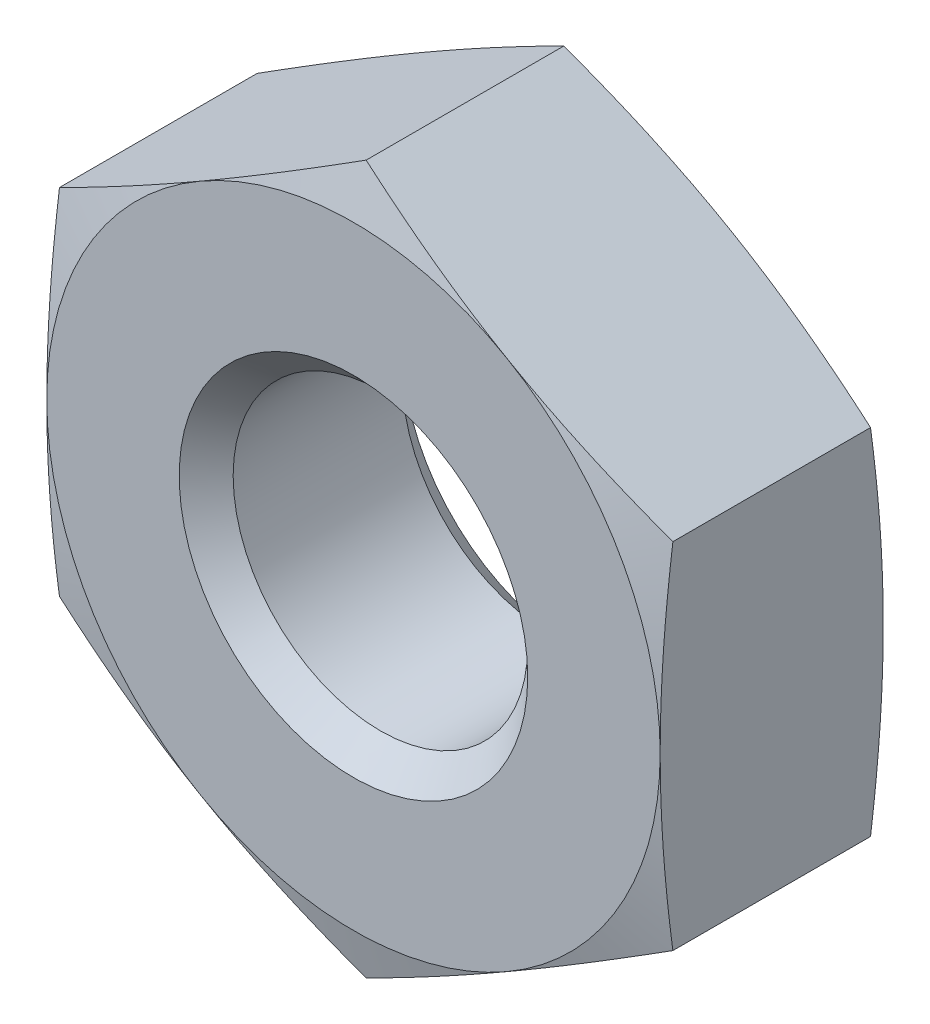
SolidWorks part; units mm, degrees
material "Plain Carbon Steel"
ref_plane "Front Plane" through (0, 0, 0) normal (0, 0, 1) x (1, 0, 0)
ref_plane "Top Plane" through (0, 0, 0) normal (0, 1, 0) x (1, 0, 0)
ref_plane "Right Plane" through (0, 0, 0) normal (1, 0, 0) x (0, 0, -1)
sketch "Sketch1" plane through (0, 0, 0) normal (1, 0, 0) x (0, 0, -1)
  line L0 (0, 0) -> (0, 5.588)
  line L1 (0, 5.588) -> (0.2995, 6.7056)
  line L2 (0.2995, 6.7056) -> (3.7645, 6.7056)
  line L3 (3.7645, 6.7056) -> (4.064, 5.588)
  line L4 (4.064, 5.588) -> (4.064, 0)
  line L5 (4.064, 0) -> (0, 0)
  line L6 (4.064, 0) -> (0, 0) construction
sketch "Sketch2" plane through (0, 0, 0) normal (0, 0, 1) x (1, 0, 0)
  line L0 (-11.176, 11.176) -> (-11.176, -11.176)
  line L1 (-11.176, -11.176) -> (11.176, -11.176)
  line L2 (11.176, -11.176) -> (11.176, 11.176)
  line L3 (11.176, 11.176) -> (-11.176, 11.176)
  line L4 (-5.588, 3.2262) -> (-5.588, -3.2262)
  line L5 (-5.588, -3.2262) -> (0, -6.4525)
  line L6 (0, -6.4525) -> (5.588, -3.2262)
  line L7 (5.588, -3.2262) -> (5.588, 3.2262)
  line L8 (5.588, 3.2262) -> (0, 6.4525)
  line L9 (0, 6.4525) -> (-5.588, 3.2262)
revolve "Revolve1" add sketch "Sketch1" angle 360 about L6 reverse direction yes
extrude "Cut-Extrude1" cut sketch "Sketch2" against normal blind 4.064
sketch "Sketch3" plane through (0, 0, 0) normal (1, 0, 0) x (0, 0, -1)
  line L0 (0, 0) -> (0, 3.175)
  line L1 (0, 3.175) -> (0.4915, 2.6835)
  line L2 (0.4915, 2.6835) -> (3.5725, 2.6835)
  line L3 (3.5725, 2.6835) -> (4.064, 3.175)
  line L4 (4.064, 3.175) -> (4.064, 0)
  line L5 (4.064, 0) -> (0, 0)
  line L6 (4.064, 0) -> (0, 0) construction
revolve "Cut-Revolve1" cut sketch "Sketch3" angle 360 about L6 reverse direction yes
cosmetic thread "Cosmetic Thread1" parameters "D1"=4.064, "D2"=6.35
ref_plane "NUT XY" through (0, 0, 0) normal (0, 0, 1) x (1, 0, 0)
ref_plane "NUT XZ" through (0, 0, 0) normal (0, -1, 0) x (-1, 0, 0)
ref_plane "NUT YZ" through (0, 0, 0) normal (1, 0, 0) x (0, 0, -1)
ref_axis "NUT X" through (-80.9, 0, 0) along (1, 0, 0)
ref_axis "NUT Y" through (0, -50, 0) along (0, 1, 0)
ref_axis "NUT Z" through (0, 0, 80.9) along (0, 0, -1)
sketch3d "NUT"
  point P0 (0, 0, 0)
ref_plane "a1 XY" through (0, 0, 0) normal (0, 0, 1) x (1, 0, 0)
ref_plane "a1 XZ" through (0, 5.588, 0) normal (0, -1, 0) x (-1, 0, 0)
ref_plane "a1 YZ" through (-5.588, 0, 0) normal (1, 0, 0) x (0, 0, -1)
ref_axis "a1 X" through (-80.9, 5.588, 0) along (1, 0, 0)
ref_axis "a1 Y" through (-5.588, -50, 0) along (0, 1, 0)
ref_axis "a1 Z" through (-5.588, 5.588, 80.9) along (0, 0, -1)
sketch3d "a1"
  point P0 (-5.588, 5.588, 0)
ref_plane "a2 XY" through (0, 0, 0) normal (0, 0, 1) x (1, 0, 0)
ref_plane "a2 XZ" through (0, 5.588, 0) normal (0, -1, 0) x (-1, 0, 0)
ref_plane "a2 YZ" through (5.588, 0, 0) normal (1, 0, 0) x (0, 0, -1)
ref_axis "a2 X" through (-80.9, 5.588, 0) along (1, 0, 0)
ref_axis "a2 Y" through (5.588, -50, 0) along (0, 1, 0)
ref_axis "a2 Z" through (5.588, 5.588, 80.9) along (0, 0, -1)
sketch3d "a2"
  point P0 (5.588, 5.588, 0)
ref_plane "b1 XY" through (0, 0, 0) normal (1, 0, 0) x (0, 0, -1)
ref_plane "b1 XZ" through (0, 5.588, 0) normal (0, -1, 0) x (-1, 0, 0)
ref_plane "b1 YZ" through (0, 0, 0) normal (0, 0, -1) x (-1, 0, 0)
ref_axis "b1 X" through (0, 5.588, 80.9) along (0, 0, -1)
ref_axis "b1 Y" through (0, -50, 0) along (0, 1, 0)
ref_axis "b1 Z" through (80.9, 5.588, 0) along (-1, 0, 0)
sketch3d "b1"
  point P0 (0, 5.588, 0)
ref_plane "b2 XY" through (0, 0, 0) normal (1, 0, 0) x (0, 0, -1)
ref_plane "b2 XZ" through (0, 5.588, 0) normal (0, -1, 0) x (-1, 0, 0)
ref_plane "b2 YZ" through (0, 0, -4.064) normal (0, 0, -1) x (-1, 0, 0)
ref_axis "b2 X" through (0, 5.588, 80.9) along (0, 0, -1)
ref_axis "b2 Y" through (0, -50, -4.064) along (0, 1, 0)
ref_axis "b2 Z" through (80.9, 5.588, -4.064) along (-1, 0, 0)
sketch3d "b2"
  point P0 (0, 5.588, -4.064)
ref_plane "e XY" through (0, 0, 0) normal (1, 0, 0) x (0, 0, -1)
ref_plane "e XZ" through (0, 0, 0) normal (0, -1, 0) x (-1, 0, 0)
ref_plane "e YZ" through (0, 0, -4.064) normal (0, 0, -1) x (-1, 0, 0)
ref_axis "e X" through (0, 0, 80.9) along (0, 0, -1)
ref_axis "e Y" through (0, -50, -4.064) along (0, 1, 0)
ref_axis "e Z" through (80.9, 0, -4.064) along (-1, 0, 0)
sketch3d "e"
  point P0 (0, 0, -4.064)
ref_plane "ol1 XY" through (0, 0, 0) normal (0, 1, 0) x (1, 0, 0)
ref_plane "ol1 XZ" through (0, 0, -5.588) normal (0, 0, 1) x (1, 0, 0)
ref_plane "ol1 YZ" through (0, 0, 0) normal (1, 0, 0) x (0, 0, -1)
ref_axis "ol1 X" through (-80.9, 0, -5.588) along (1, 0, 0)
ref_axis "ol1 Y" through (0, 0, 50) along (0, 0, -1)
ref_axis "ol1 Z" through (0, 50, -5.588) along (0, -1, 0)
sketch3d "ol1"
  point P0 (0, 0, -5.588)
ref_plane "ol2 XY" through (0, 0, 0) normal (0, 1, 0) x (1, 0, 0)
ref_plane "ol2 XZ" through (0, 0, -5.588) normal (0, 0, 1) x (1, 0, 0)
ref_plane "ol2 YZ" through (4.064, 0, 0) normal (1, 0, 0) x (0, 0, -1)
ref_axis "ol2 X" through (-80.9, 0, -5.588) along (1, 0, 0)
ref_axis "ol2 Y" through (4.064, 0, 50) along (0, 0, -1)
ref_axis "ol2 Z" through (4.064, 50, -5.588) along (0, -1, 0)
sketch3d "ol2"
  point P0 (4.064, 0, -5.588)
ref_plane "th1 XY" through (0, 0, 0) normal (1, 0, 0) x (0, 0, -1)
ref_plane "th1 XZ" through (0, 3.175, 0) normal (0, -1, 0) x (-1, 0, 0)
ref_plane "th1 YZ" through (0, 0, -4.064) normal (0, 0, -1) x (-1, 0, 0)
ref_axis "th1 X" through (0, 3.175, 80.9) along (0, 0, -1)
ref_axis "th1 Y" through (0, -50, -4.064) along (0, 1, 0)
ref_axis "th1 Z" through (80.9, 3.175, -4.064) along (-1, 0, 0)
sketch3d "th1"
  point P0 (0, 3.175, -4.064)
ref_plane "th2 XY" through (0, 0, 0) normal (1, 0, 0) x (0, 0, -1)
ref_plane "th2 XZ" through (0, -3.175, 0) normal (0, -1, 0) x (-1, 0, 0)
ref_plane "th2 YZ" through (0, 0, -4.064) normal (0, 0, -1) x (-1, 0, 0)
ref_axis "th2 X" through (0, -3.175, 80.9) along (0, 0, -1)
ref_axis "th2 Y" through (0, -50, -4.064) along (0, 1, 0)
ref_axis "th2 Z" through (80.9, -3.175, -4.064) along (-1, 0, 0)
sketch3d "th2"
  point P0 (0, -3.175, -4.064)
